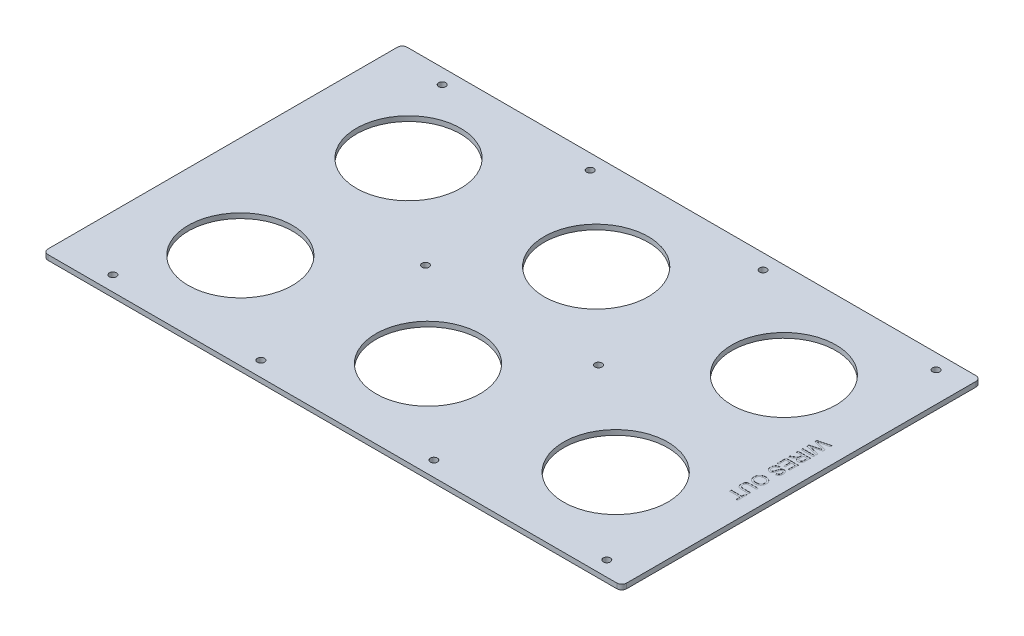
SolidWorks part; units mm, degrees
material "ABS"
ref_plane "Front" through (0, 0, 0) normal (0, 0, 1) x (1, 0, 0)
ref_plane "Top" through (0, 0, 0) normal (0, 1, 0) x (1, 0, 0)
ref_plane "Right" through (0, 0, 0) normal (1, 0, 0) x (0, 0, -1)
sketch "Sketch1" plane through (0, 0, 0) normal (0, 1, 0) x (1, 0, 0)
  line L1 (-180.975, 114.3) -> (180.975, 114.3)
  line L2 (-184.15, 111.125) -> (-184.15, -111.125)
  line L3 (-180.975, -114.3) -> (180.975, -114.3)
  line L4 (184.15, 111.125) -> (184.15, -111.125)
  line L5 (-184.15, 114.3) -> (184.15, -114.3) construction
  line L6 (-184.15, -114.3) -> (184.15, 114.3) construction
  circle A0 centre (119.5086, -53.5178) radius 33.147
  arc A1 (-184.15, -111.125) -> (-180.975, -114.3) centre (-180.975, -111.125) ccw
  arc A2 (180.975, -114.3) -> (184.15, -111.125) centre (180.975, -111.125) ccw
  arc A3 (184.15, 111.125) -> (180.975, 114.3) centre (180.975, 111.125) ccw
  arc A4 (-180.975, 114.3) -> (-184.15, 111.125) centre (-180.975, 111.125) ccw
  circle A21 centre (-55.0333, 0) radius 2.2479 construction
  circle A22 centre (55.0333, 0) radius 2.2479 construction
  circle A23 centre (-55.0333, 0) radius 2.2479
  circle A24 centre (55.0333, 0) radius 2.2479
  circle A25 centre (119.5086, 53.5178) radius 33.147
  circle A26 centre (0.0643, 53.5178) radius 33.147
  circle A27 centre (0.0643, -53.5178) radius 33.147
  circle A28 centre (-119.38, 53.5178) radius 33.147
  circle A29 centre (-119.38, -53.5178) radius 33.147
  arc A34 (-143.7521, 103.8733) -> (-143.7521, 3.1623) centre (-119.38, 53.5178) ccw construction
  arc A35 (-24.3078, 103.8733) -> (-24.3078, 3.1623) centre (0.0643, 53.5178) ccw construction
  arc A36 (95.1365, 103.8733) -> (95.1365, 3.1623) centre (119.5086, 53.5178) ccw construction
  arc A37 (-143.7521, -3.1623) -> (-143.7521, -103.8733) centre (-119.38, -53.5178) ccw construction
  arc A38 (-24.3078, -3.1623) -> (-24.3078, -103.8733) centre (0.0643, -53.5178) ccw construction
  arc A39 (95.1365, -3.1623) -> (95.1365, -103.8733) centre (119.5086, -53.5178) ccw construction
  circle A40 centre (-149.225, -104.775) radius 2.2479 construction
  circle A41 centre (-55.0333, -104.775) radius 2.2479 construction
  circle A42 centre (55.0333, -104.775) radius 2.2479 construction
  circle A43 centre (165.1, -104.775) radius 2.2479 construction
  circle A44 centre (-149.225, 104.775) radius 2.2479 construction
  circle A45 centre (-55.0333, 104.775) radius 2.2479 construction
  circle A46 centre (55.0333, 104.775) radius 2.2479 construction
  circle A47 centre (165.1, 104.775) radius 2.2479 construction
  circle A48 centre (-149.225, -104.775) radius 2.2479
  circle A49 centre (-55.0333, -104.775) radius 2.2479
  circle A50 centre (55.0333, -104.775) radius 2.2479
  circle A51 centre (165.1, -104.775) radius 2.2479
  circle A52 centre (-149.225, 104.775) radius 2.2479
  circle A53 centre (-55.0333, 104.775) radius 2.2479
  circle A54 centre (55.0333, 104.775) radius 2.2479
  circle A55 centre (165.1, 104.775) radius 2.2479
  point P0 (0, 0)
  dimension "D3" = 66.294
  dimension "D4" = 3.175
  dimension "D1" = 368.3
  dimension "D2" = 228.6
extrude "Boss-Extrude1" add sketch "Sketch1" along normal blind 3.175
sketch "Sketch2" plane through (0, 3.175, 0) normal (0, 1, 0) x (1, 0, 0)
  line L0 (166.15, 30) -> (166.15, -30) construction
  line L1 (0, 0) -> (184.15, 0) construction
  line L2 (184.15, -111.125) -> (184.15, 111.125) construction
  text T0 "WIRES OUT" font "Arial" height in points 30
  point P7 (166.15, 0)
  dimension "D1" = 18
  dimension "D2" = 60
extrude "Cut-Extrude1" cut sketch "Sketch2" against normal blind 0.1
